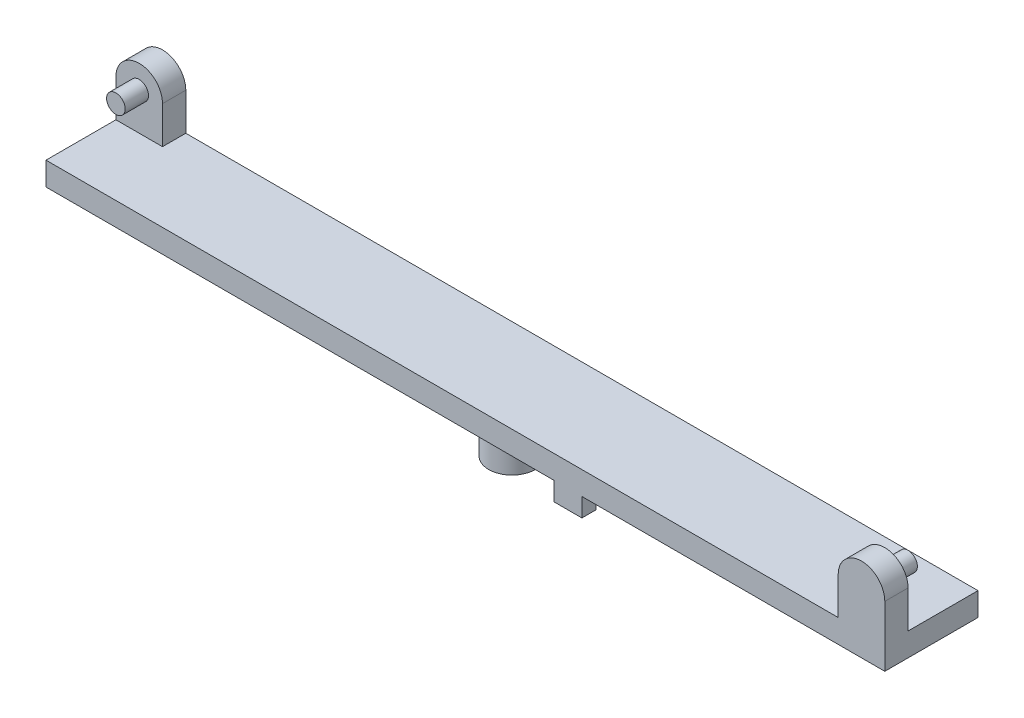
SolidWorks part; units mm, degrees
material "1060 Alloy"
ref_plane "Front Plane" through (0, 0, 0) normal (0, 0, 1) x (1, 0, 0)
ref_plane "Top Plane" through (0, 0, 0) normal (0, 1, 0) x (1, 0, 0)
ref_plane "Right Plane" through (0, 0, 0) normal (1, 0, 0) x (0, 0, -1)
sketch "Sketch1" plane through (0, 0, 0) normal (0, 1, 0) x (1, 0, 0)
  line L1 (-90, -10) -> (90, -10)
  line L2 (-90, -10) -> (-90, 10)
  line L3 (-90, 10) -> (90, 10)
  line L4 (90, -10) -> (90, 10)
  line L5 (-90, -10) -> (90, 10) construction
  line L6 (-90, 10) -> (90, -10) construction
  circle A0 centre (0, 0) radius 5
  point P0 (0, 0)
  dimension "D1" = 10
  dimension "D2" = 180
  dimension "D3" = 20
extrude "Boss-Extrude1" add sketch "Sketch1" along normal blind 5 contours A0 | L1 L4 L3 L2 A0 region at (-88.1889, 0, 0) region at (0, 0, 0)
sketch "Sketch2" plane through (0, 0, 0) normal (0, 0, 1) x (1, 0, 0)
  line L0 (-90, 5) -> (-90, 13)
  line L1 (-80, 13) -> (-80, 5)
  line L2 (-90, 5) -> (90, 5) construction
  line L3 (-80, 5) -> (-90, 5)
  line L4 (0, 0) -> (0, 36.422) construction
  line L5 (80, 5) -> (90, 5)
  line L6 (80, 13) -> (80, 5)
  line L7 (90, 5) -> (90, 13)
  arc A0 (-90, 13) -> (-80, 13) centre (-85, 13) cw
  circle A1 centre (-85, 13) radius 2
  circle A2 centre (85, 13) radius 2
  arc A3 (90, 13) -> (80, 13) centre (85, 13) ccw
  dimension "D3" = 4
  dimension "D1" = 10
  dimension "D2" = 8
extrude "Boss-Extrude4" add sketch "Sketch2" along normal blind 5 from offset 10 contours A0 L0 L3 L1 A1 | A1 region at (-85, 10.782, 0) region at (-85, 13, 0) offset against normal yes
extrude "Boss-Extrude5" add sketch "Sketch2<3>" against normal up to surface (5 mm away) contours A1 region at (-85, 13, 0) up to face at (-83.75, 9.25, -5)
sketch "Sketch2<3>" plane through (0, 0, 0) normal (0, 0, 1) x (1, 0, 0) same geometry as "Sketch2"
extrude "Boss-Extrude6" add sketch "Sketch2<4>" against normal blind 5 from offset 10 contours L7 A3 L6 L5 A2 | A2 region at (85, 10.782, 0) region at (85, 13, 0)
sketch "Sketch2<4>" plane through (0, 0, 0) normal (0, 0, 1) x (1, 0, 0) same geometry as "Sketch2"
extrude "Boss-Extrude7" add sketch "Sketch2<5>" along normal blind 5 contours A2 region at (85, 13, 0)
sketch "Sketch2<5>" plane through (0, 0, 0) normal (0, 0, 1) x (1, 0, 0) same geometry as "Sketch2"
extrude "Boss-Extrude8" add sketch "Sketch1<3>" against normal blind 10 contours A0 region at (0, 0, 0)
sketch "Sketch1<3>" plane through (0, 0, 0) normal (0, 1, 0) x (1, 0, 0) same geometry as "Sketch1"
sketch "Sketch3" plane through (0, 0, 10) normal (0, 0, 1) x (1, 0, 0)
  line L0 (-90, 0) -> (90, 0) construction
  line L1 (19, 0) -> (25, 0)
  line L2 (19, 0) -> (19, -4)
  line L3 (19, -4) -> (25, -4)
  line L4 (25, 0) -> (25, -4)
  line L5 (90, 13) -> (90, 0) construction
  dimension "D1" = 4
  dimension "D2" = 6
  dimension "D3" = 65
extrude "Boss-Extrude9" add sketch "Sketch3" against normal blind 3
